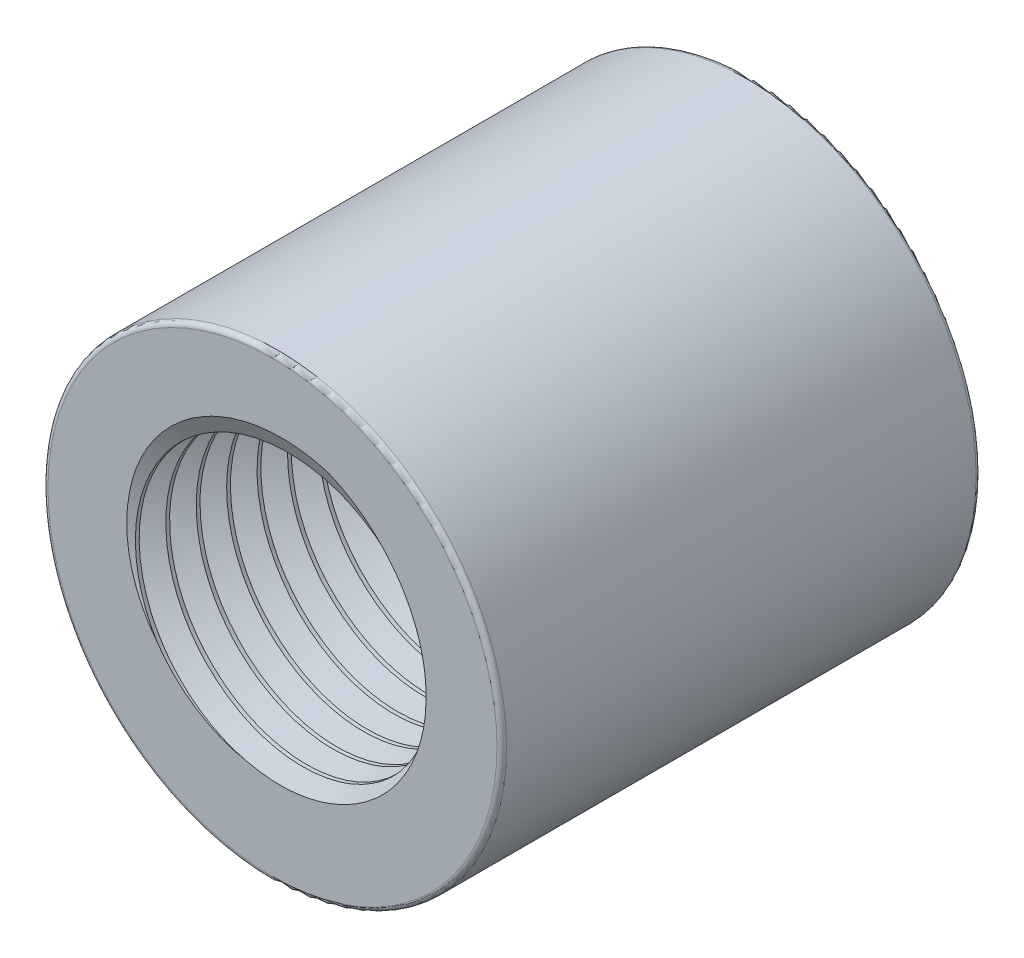
SolidWorks part; units mm, degrees
ref_plane "Front" through (0, 0, 0) normal (0, 0, 1) x (1, 0, 0)
ref_plane "Top" through (0, 0, 0) normal (0, 1, 0) x (1, 0, 0)
ref_plane "Right" through (0, 0, 0) normal (1, 0, 0) x (0, 0, -1)
sketch "Sketch1" plane through (0, 0, 0) normal (0, 0, 1) x (1, 0, 0)
  circle A0 centre (-0.5181, -0.1295) radius 9.5719
  circle A1 centre (-0.5181, -0.1295) radius 5.8421
extrude "Boss-Extrude1" add sketch "Sketch1" along normal blind 20
sketch "Sketch2" plane through (0, 0, 0) normal (0, 0, -1) x (-1, 0, 0)
  circle A0 centre (0.5181, -0.1295) radius 5.8421 construction
  circle A1 centre (0.5181, -0.1295) radius 5.8421
curve "Helix/Spiral1" pitch 1.27 height 10.16 radius 5.8421 centre (-0.5181, -0.1295, 0) axis (0, 0, 1) start towards (0.7071, 0.7071, 0)
ref_plane "Plane1" through (3.6129, 4.0015, 0) normal (-0.7067, 0.7067, 0.0346) x (0.7075, 0.7058, 0.0345)
sketch "Sketch3" plane through (3.6129, 4.0015, 0) normal (-0.7067, 0.7067, 0.0346) x (0.7075, 0.7058, 0.0345)
  line L1 (-0.3369, -0.7993) -> (0.7474, -0.1575)
  line L2 (0.7474, -0.1575) -> (-0.3506, 0.4606)
  line L3 (-0.3506, 0.4606) -> (-0.3369, -0.7993)
  circle A0 centre (0.02, -0.1654) radius 0.3637 construction
  point P1 (0, 0)
  point P6 (0.173, -0.1525)
  dimension "D1" = 1.26
sweep "Cut-Sweep2" cut profiles "Sketch3" path "Helix/Spiral1" align with end faces yes
sketch "Sketch4" plane through (0, 0, 20) normal (0, 0, 1) x (1, 0, 0)
  circle A0 centre (-0.5181, -0.1295) radius 5.8421 construction
  circle A1 centre (-0.5181, -0.1295) radius 5.8421
curve "Helix/Spiral2" pitch 1.27 height 10.16 radius 5.8421 centre (-0.5181, -0.1295, 20) axis (0, 0, -1) start towards (-0.7071, 0.7071, 0)
ref_plane "Plane2" through (-4.6491, 4.0015, 20) normal (0.7067, 0.7067, -0.0346) x (0.7075, -0.7058, 0.0345)
sketch "Sketch5" plane through (-4.6491, 4.0015, 20) normal (0.7067, 0.7067, -0.0346) x (0.7075, -0.7058, 0.0345)
  line L1 (0.1393, -0.8932) -> (0.1393, 0.3668)
  line L2 (0.1393, 0.3668) -> (-0.9519, -0.2632)
  line L3 (-0.9519, -0.2632) -> (0.1393, -0.8932)
  circle A0 centre (-0.2245, -0.2632) radius 0.3637 construction
  point P1 (-0.2245, -0.2632)
  dimension "D1" = 1.26
sweep "Cut-Sweep3" cut profiles "Sketch5" path "Helix/Spiral2" align with end faces yes
fillet "Fillet1" radius 0.2 2 edges at (9.0538, -0.1295, 0) (9.0538, -0.1295, 20)
